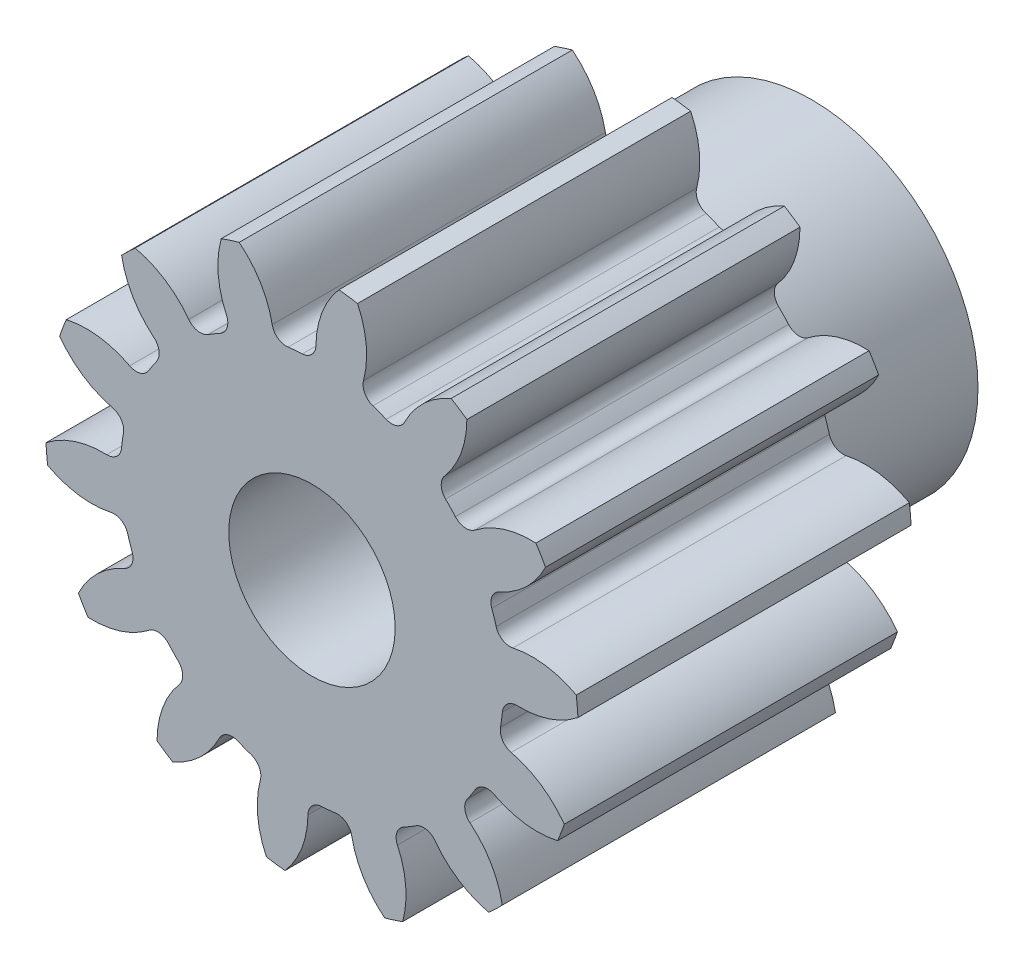
SolidWorks part; units mm, degrees
ref_plane "Front" through (0, 0, 0) normal (0, 0, 1) x (1, 0, 0)
ref_plane "Top" through (0, 0, 0) normal (0, 1, 0) x (1, 0, 0)
ref_plane "Right" through (0, 0, 0) normal (1, 0, 0) x (0, 0, -1)
sketch "Sketch3" plane through (0, 0, 0) normal (0, 0, 1) x (1, 0, 0)
  circle A0 centre (0, 0) radius 8
  dimension "od" = 16
extrude "gearBody" add sketch "Sketch3" along normal blind 10.0076
sketch "Sketch2" plane through (0, 0, 0) normal (0, 0, 1) x (1, 0, 0)
  line L0 (0, 0) -> (6.2612, 2.5935) construction
  line L1 (7.9605, -3.2999) -> (0, 0) construction
  line L2 (0, 0) -> (36.3143, 0) construction
  line L3 (6.9995, -0.0841) -> (6.7623, -1.8085) construction
  line L5 (6.8809, -0.9463) -> (0, 0) construction
  line L7 (0, 0) -> (6.777, 0) construction
  arc A0 (6.7757, -0.136) -> (6.5608, -1.6982) centre (0, 0) ccw construction
  arc A1 (7.989, 0.4188) -> (7.5794, -2.5599) centre (0, 0) ccw construction
  arc A2 (6.9995, -0.0841) -> (6.7623, -1.8085) centre (0, 0) ccw construction
  arc A3 (5.6624, -0.9951) -> (5.7208, -0.5705) centre (0, 0) ccw
  arc A4 (7.9605, -3.2999) -> (5.9851, -1.4886) centre (5.3286, -4.1874) ccw
  arc A5 (7.9605, -3.2999) -> (8.5558, 1.0284) centre (0, 0) ccw
  arc A6 (8.5558, 1.0284) -> (6.1648, -0.1824) centre (6.2612, 2.5935) cw
  arc A7 (5.7208, -0.5705) -> (6.1648, -0.1824) centre (6.1498, -0.6132) cw
  arc A8 (5.9851, -1.4886) -> (5.6624, -0.9951) centre (6.087, -1.0697) cw
  point P6 (8.5558, 1.0284)
  point P22 (7.9605, -3.2999)
  dimension "baseDia" = 13.5541
  dimension "od" = 16
  dimension "pd" = 14
  dimension "rd" = 11.4984
  dimension "rFillet" = 0.4311
  dimension "pointX" = 8.5558
  dimension "pointY" = 1.0284
  dimension "CTT" = 1.7244
  dimension "flankCenterAngle" = 22.5
extrude "toothCut" cut sketch "Sketch2" along normal through all
pattern_circular "CirPattern1" count 14 over 360 about axis through (0, 0, 10.0076) along (0, 0, -1) of "toothCut"
ref_axis "toothSpace" through (0, 0, 0) along (0.9907, -0.1362, 0)
ref_axis "Axis2" through (7.4841, -2.8262, 0) along (-0.9355, 0.3533, 0)
sketch "hub1Dia" plane through (0, 0, 0) normal (0, 0, -1) x (-1, 0, 0)
  circle A0 centre (0, 0) radius 5
  dimension "hub1Dia" = 10
extrude "hub1" add sketch "hub1Dia" along normal blind 5
sketch "hub2Dia" plane through (0, 0, 10.0076) normal (0, 0, 1) x (1, 0, 0)
  circle A0 centre (0, 0) radius 0.5
  dimension "hub2dia" = 1
sketch "boreDia" plane through (0, 0, 0) normal (0, 0, 1) x (1, 0, 0)
  circle A0 centre (0, 0) radius 2.5
  dimension "boreDia" = 5
extrude "bore" cut sketch "boreDia" against normal mid plane 25400
sketch "kwy1sketch" plane through (0, 0, 0) normal (0, 0, 1) x (1, 0, 0)
  line L0 (-5.147, 1.5151) -> (0, 0) construction
  line L1 (3.4987, -0.5087) -> (3.2164, -1.468)
  line L2 (3.2164, -1.468) -> (2.0172, -1.115)
  line L3 (3.4987, -0.5087) -> (2.2996, -0.1557)
  line L4 (2.0172, -1.115) -> (0, 0)
  line L5 (0, 0) -> (2.2996, -0.1557)
  line L6 (0, 0) -> (5.6956, -0.7833) construction
  line L7 (3.3576, -0.9883) -> (0, 0) construction
  arc A7 (5.6624, -0.9951) -> (5.7208, -0.5705) centre (0, 0) ccw construction
  point P9 (3.3576, -0.9883)
  point P13 (-0.8586, 0.2527)
  dimension "kwy1width" = 1
  dimension "kwy1depth" = 3.5
  dimension "kwy1angle" = 8.571
  dimension "kwy1Depth2" = 1.25
sketch "kwy2sketch" plane through (0, 0, 0) normal (0, 0, 1) x (1, 0, 0)
  line L0 (5.6956, -0.7833) -> (0, 0) construction
  line L1 (0, 0) -> (-3.2553, -1.7747) construction
  line L2 (2.8337, 2.1143) -> (3.3123, 1.2363)
  line L3 (3.3123, 1.2363) -> (2.2148, 0.638)
  line L4 (2.8337, 2.1143) -> (1.7362, 1.516)
  line L5 (2.2148, 0.638) -> (0, 0)
  line L6 (0, 0) -> (1.7362, 1.516)
  arc A2 (5.6624, -0.9951) -> (5.7208, -0.5705) centre (0, 0) ccw construction
  point P10 (3.073, 1.6753)
  dimension "kwy2angle" = 36.429
  dimension "kwy2Width" = 1
  dimension "kwy2depth" = 3.5
  dimension "kwy2Depth2" = 1.25
sketch "kwy3sketch" plane through (0, 0, 0) normal (0, 0, 1) x (1, 0, 0)
  line L0 (5.6956, -0.7833) -> (0, 0) construction
  line L1 (0, 0) -> (-0.7574, -2.5732) construction
  line L2 (0.5087, 3.4987) -> (1.468, 3.2164)
  line L3 (1.468, 3.2164) -> (1.115, 2.0172)
  line L4 (0.5087, 3.4987) -> (0.1557, 2.2996)
  line L5 (1.115, 2.0172) -> (0, 0)
  line L6 (0.1557, 2.2996) -> (0, 0)
  point P10 (0.9883, 3.3576)
  dimension "kwy3angle" = 81.429
  dimension "kwy3depth" = 3.5
  dimension "kwy3width" = 1
  dimension "kwy3Depth2" = 1.25
sketch "kwy4sketch" plane through (0, 0, 0) normal (0, 0, 1) x (1, 0, 0)
  line L0 (5.6956, -0.7833) -> (0, 0) construction
  line L1 (0, 0) -> (1.0039, -1.8414) construction
  line L2 (-1.2363, 3.3123) -> (-2.1143, 2.8337)
  line L3 (-2.1143, 2.8337) -> (-1.516, 1.7362)
  line L4 (-1.516, 1.7362) -> (0, 0)
  line L5 (-0.638, 2.2148) -> (0, 0)
  line L6 (-1.2363, 3.3123) -> (-0.638, 2.2148)
  point P15 (-1.6753, 3.073)
  dimension "kwy4angle" = 126.429
  dimension "kwy4depth" = 3.5
  dimension "kwy4width" = 1
  dimension "kwy4Depth2" = 1.25
sketch "kwy5sketch" plane through (0, 0, 0) normal (0, 0, 1) x (1, 0, 0)
  line L0 (5.6956, -0.7833) -> (0, 0) construction
  line L1 (0, 0) -> (1.7279, -0.5086) construction
  line L2 (-3.2164, 1.468) -> (-3.4987, 0.5087)
  line L3 (-3.4987, 0.5087) -> (-2.2996, 0.1557)
  line L4 (-3.2164, 1.468) -> (-2.0172, 1.115)
  line L5 (-2.2996, 0.1557) -> (0, 0)
  line L6 (-2.0172, 1.115) -> (0, 0)
  point P10 (-3.3576, 0.9883)
  dimension "kwy5width" = 1
  dimension "kwy5depth" = 3.5
  dimension "kwy5angle" = 171.429
  dimension "kwy5Depth2" = 1.25
sketch "kwy6sketch" plane through (0, 0, 0) normal (0, 0, 1) x (1, 0, 0)
  line L0 (5.6956, -0.7833) -> (0, 0) construction
  line L1 (0, 0) -> (1.5802, 0.8615) construction
  line L2 (-3.3123, -1.2363) -> (-2.8337, -2.1143)
  line L3 (-2.8337, -2.1143) -> (-1.7362, -1.516)
  line L4 (-3.3123, -1.2363) -> (-2.2148, -0.638)
  line L5 (-1.7362, -1.516) -> (0, 0)
  line L6 (-2.2148, -0.638) -> (0, 0)
  point P10 (-3.073, -1.6753)
  dimension "kwy6angle" = 216.429
  dimension "kwy6width" = 1
  dimension "kwy6depth" = 3.5
  dimension "kwy6Depth2" = 1.25
sketch "kwy7sketch" plane through (0, 0, 0) normal (0, 0, 1) x (1, 0, 0)
  line L0 (5.6956, -0.7833) -> (0, 0) construction
  line L1 (0, 0) -> (0.5694, 1.9343) construction
  line L2 (-1.468, -3.2164) -> (-0.5087, -3.4987)
  line L3 (-1.468, -3.2164) -> (-1.115, -2.0172)
  line L4 (-0.5087, -3.4987) -> (-0.1557, -2.2996)
  line L5 (-1.115, -2.0172) -> (0, 0)
  line L6 (-0.1557, -2.2996) -> (0, 0)
  point P10 (-0.9883, -3.3576)
  dimension "kwy7angle" = 81.429
  dimension "kwy7width" = 1
  dimension "kwy7depth" = 3.5
  dimension "kwy7angle1" = 261.429
  dimension "kwy7Depth2" = 1.25
sketch "kwy8sketch" plane through (0, 0, 0) normal (0, 0, 1) x (1, 0, 0)
  line L0 (5.6956, -0.7833) -> (0, 0) construction
  line L1 (0, 0) -> (-0.8575, 1.5729) construction
  line L2 (1.2363, -3.3123) -> (2.1143, -2.8337)
  line L3 (2.1143, -2.8337) -> (1.516, -1.7362)
  line L4 (1.2363, -3.3123) -> (0.638, -2.2148)
  line L5 (1.516, -1.7362) -> (0, 0)
  line L6 (0.638, -2.2148) -> (0, 0)
  point P10 (1.6753, -3.073)
  dimension "kwy8angle" = 306.429
  dimension "kwy8width" = 1
  dimension "kwy8depth" = 3.5
  dimension "kwy8Depth2" = 1.25
sketch "centerLine" plane through (0, 0, 0) normal (0, 1, 0) x (1, 0, 0)
  line L0 (0, 36.4807) -> (0, -59.6309) construction
ref_plane "CB1plane" through (0, 0, -5) normal (0, 0, -1) x (-1, 0, 0)
sketch "CB1diameter" plane through (0, 0, -5) normal (0, 0, -1) x (-1, 0, 0)
  circle A0 centre (0, 0) radius 0.5
  dimension "CB1diameter" = 1
ref_plane "CB2plane" through (0, 0, 10.0076) normal (0, 0, 1) x (1, 0, 0)
sketch "CB2diameter" plane through (0, 0, 10.0076) normal (0, 0, 1) x (1, 0, 0)
  circle A0 centre (0, 0) radius 0.5
  dimension "CB2diameter" = 1
ref_axis "Axis1" through (0, 0, 50) along (0, 0, -1)
sketch3d "3DSketch1" plane through (0, 0, 0) normal (0, 0, 1) x (1, 0, 0)
